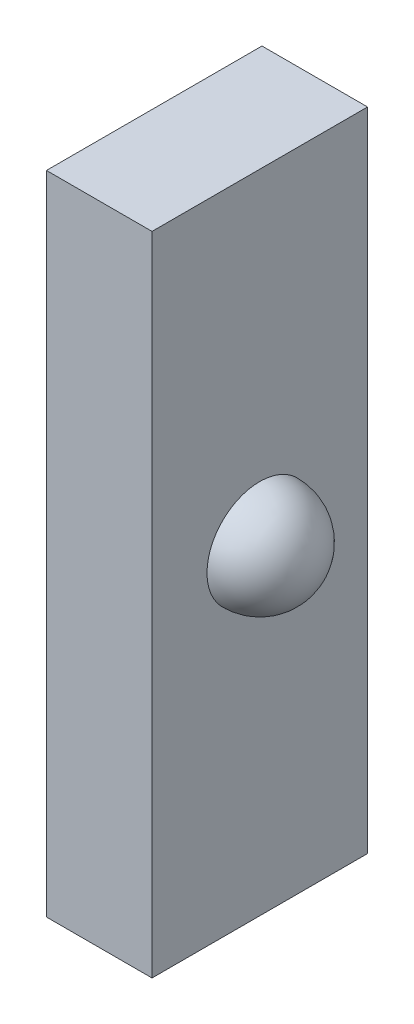
SolidWorks part; units mm, degrees
ref_plane "前视基准面" through (0, 0, 0) normal (0, 0, 1) x (1, 0, 0)
ref_plane "上视基准面" through (0, 0, 0) normal (0, 1, 0) x (1, 0, 0)
ref_plane "右视基准面" through (0, 0, 0) normal (1, 0, 0) x (0, 0, -1)
other "Configuration Table"
sketch "草图1" plane through (0, 0, 0) normal (1, 0, 0) x (0, 0, -1)
  line L0 (0, 4.9) -> (0, -4.9)
  arc A0 (0, -4.9) -> (0, 4.9) centre (0, 0) ccw
  dimension "D1" = 4.9
revolve "旋转1" add sketch "草图1" angle 180 about L0
sketch "草图5" plane through (0, 0, 0) normal (0, 0, 1) x (1, 0, 0)
  line L1 (-9.7969, 30) -> (0, 30)
  line L2 (-9.7969, 30) -> (-9.7969, -30)
  line L3 (-9.7969, -30) -> (0, -30)
  line L4 (0, 30) -> (0, -30)
  point P4 (0, 22.2493)
  dimension "D1" = 60
  dimension "D2" = 30
extrude "凸台-拉伸1" add sketch "草图5" along normal blind 10 and the other way blind 10
sketch "草图7" plane through (0, 0, 0) normal (0, 0, 1) x (1, 0, 0)
  line L0 (-9.7969, 30) -> (-9.7969, -30) construction
  line L1 (-9.7969, 9.2) -> (-9.7969, -9.2)
  arc A0 (-9.7969, 9.2) -> (-9.7969, -9.2) centre (-9.7969, 0) ccw
  dimension "D1" = 9.2
revolve "切除-旋转1" cut sketch "草图7" angle 360 about L1
pattern_linear "阵列(线性)1" count 2 spacing 18.4 along (0, 1, 0) count 2 spacing 18.4 along (0, -1, 0) of "切除-旋转1" pattern seed only yes
